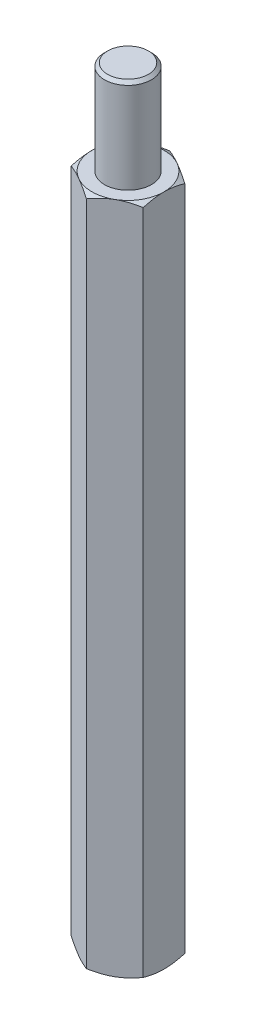
SolidWorks part; units mm, degrees
material "黄铜"
ref_plane "前视基准面" through (0, 0, 0) normal (0, 0, 1) x (1, 0, 0)
ref_plane "上视基准面" through (0, 0, 0) normal (0, 1, 0) x (1, 0, 0)
ref_plane "右视基准面" through (0, 0, 0) normal (1, 0, 0) x (0, 0, -1)
sketch "草图1" plane through (0, 0, 0) normal (0, 1, 0) x (1, 0, 0)
  line L1 (0, 2.6558) -> (-2.3, 1.3279)
  line L2 (-2.3, 1.3279) -> (-2.3, -1.3279)
  line L3 (-2.3, -1.3279) -> (0, -2.6558)
  line L4 (0, -2.6558) -> (2.3, -1.3279)
  line L5 (2.3, -1.3279) -> (2.3, 1.3279)
  line L6 (2.3, 1.3279) -> (0, 2.6558)
  circle A0 centre (0, 0) radius 2.3 construction
  dimension "六角对边宽度" = 4.6
extrude "凸台-拉伸1" add sketch "草图1" along normal blind 43
sketch "草图2" plane through (0, 43, 0) normal (0, 1, 0) x (1, 0, 0)
  circle A0 centre (0, 0) radius 1.5
  dimension "公称直径" = 3
extrude "凸台-拉伸2" add sketch "草图2" along normal blind 6
cosmetic thread "装饰螺纹线1" parameters "D2"=1
chamfer "倒角1" distance 0.2 angle 45 1 edges at (0, 49, 1.5)
sketch "草图3" plane through (0, 0, 0) normal (0, -1, 0) x (1, 0, 0)
  circle A0 centre (0, 0) radius 1.2294
  dimension "公称螺纹内径" = 2.4588
extrude "切除-拉伸1" cut sketch "草图3" against normal blind 6
cosmetic thread "装饰螺纹线2"
sketch "草图4" plane through (0, 0, 0) normal (0, -1, 0) x (1, 0, 0)
  line L0 (0, 2.6558) -> (2.3, 1.3279) construction
  circle A0 centre (0, 0) radius 2.3
extrude "切除-拉伸2" cut sketch "草图4" against normal blind 3 draft 60 flip side to cut
extrude "切除-拉伸3" cut sketch "草图4<2>" along normal blind 3 draft 60 from surface flip side to cut starting at face at (0, 43, 1.5)
sketch "草图4<2>" plane through (0, 0, 0) normal (0, -1, 0) x (1, 0, 0) same geometry as "草图4"
chamfer "倒角2" distance 0.2 angle 45 1 edges at (0, 0, -1.2294)
equation "\"D\"= 2"
equation "\"l\"= 3"
